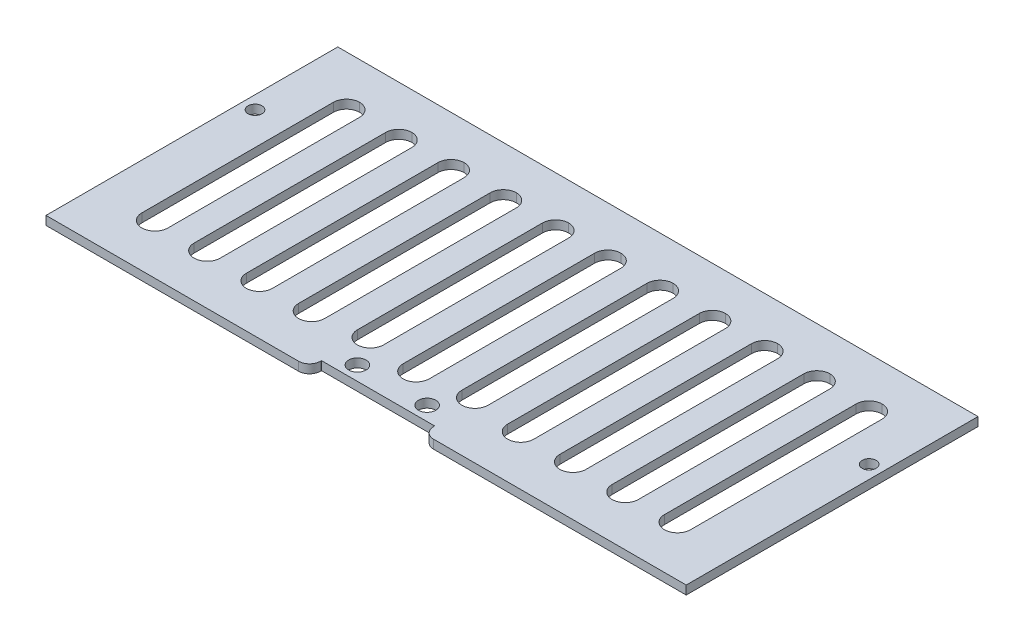
SolidWorks part; units mm, degrees
ref_plane "前视基准面" through (0, 0, 0) normal (0, 0, 1) x (1, 0, 0)
ref_plane "上视基准面" through (0, 0, 0) normal (0, 1, 0) x (1, 0, 0)
ref_plane "右视基准面" through (0, 0, 0) normal (1, 0, 0) x (0, 0, -1)
sketch "草图1" plane through (0, 0, 0) normal (0, 1, 0) x (1, 0, 0)
  line L1 (-73.5, 35) -> (73.5, 35)
  line L2 (-73.5, 35) -> (-73.5, -35)
  line L3 (-73.5, -35) -> (73.5, -35)
  line L4 (73.5, 35) -> (73.5, -35)
  line L5 (-73.5, 35) -> (73.5, -35) construction
  line L6 (-73.5, -35) -> (73.5, 35) construction
  point P0 (0, 0)
  dimension "D1" = 70
  dimension "D2" = 147
extrude "凸台-拉伸1" add sketch "草图1" along normal blind 2
sketch "草图3" plane through (0, 2, 0) normal (0, 1, 0) x (1, 0, 0)
  line L0 (73.5, -35) -> (73.5, 35) construction
  line L1 (73.5, 32) -> (-73.5, 32)
  line L2 (73.5, 32) -> (73.5, 35)
  line L3 (73.5, 35) -> (-73.5, 35)
  line L4 (-73.5, 32) -> (-73.5, 35)
  line L5 (-73.5, 35) -> (-73.5, -35) construction
  line L7 (73.5, 35) -> (-73.5, 35) construction
  dimension "D3" = 3
extrude "切除-拉伸1" cut sketch "草图3" against normal through all
sketch "草图5" plane through (0, 2, 0) normal (0, 1, 0) x (1, 0, 0)
  line L0 (0, 0) -> (0, -29) construction
  line L1 (-8, -29) -> (8, -29) construction
  circle A0 centre (-8, -29) radius 2
  circle A1 centre (8, -29) radius 2
  point P6 (0, -29)
  dimension "D3" = 4
  dimension "D4" = 4
  dimension "D1" = 16
  dimension "D2" = 29
extrude "切除-拉伸3" cut sketch "草图5" against normal blind 10
sketch "草图6" plane through (0, 2, 0) normal (0, 1, 0) x (1, 0, 0)
  line L0 (0, 32) -> (0, -35) construction
  line L1 (-73.5, 32) -> (73.5, 32) construction
  line L2 (-73.5, -35) -> (73.5, -35) construction
  line L3 (-73.5, 32) -> (-73.5, -35) construction
  circle A0 centre (-70.5, 10) radius 1.6
  circle A1 centre (70.5, 10) radius 1.6
  dimension "D1" = 3.2
  dimension "D2" = 3
  dimension "D3" = 45
extrude "切除-拉伸4" cut sketch "草图6" against normal blind 10
sketch "草图7" plane through (0, 2, 0) normal (0, 1, 0) x (1, 0, 0)
  line L0 (0, 32) -> (0, -35) construction
  line L1 (-73.5, 32) -> (73.5, 32) construction
  line L2 (-73.5, -35) -> (73.5, -35) construction
  line L3 (9, -25) -> (9, 23.5)
  line L4 (-3, -26.5) -> (3, -26.5)
  line L5 (-3, -26.5) -> (-3, 23.5)
  line L6 (-3, 23.5) -> (3, 23.5)
  line L7 (3, -26.5) -> (3, 23.5)
  line L8 (-3, -26.5) -> (3, 23.5) construction
  line L9 (-3, 23.5) -> (3, -26.5) construction
  line L11 (15, -25) -> (15, 23.5)
  line L12 (9, 23.5) -> (15, 23.5)
  line L13 (21, -26.5) -> (21, 23.5)
  line L14 (21, -26.5) -> (27, -26.5)
  line L15 (27, -26.5) -> (27, 23.5)
  line L16 (21, 23.5) -> (27, 23.5)
  line L17 (33, -26.5) -> (33, 23.5)
  line L18 (33, -26.5) -> (39, -26.5)
  line L19 (39, -26.5) -> (39, 23.5)
  line L20 (33, 23.5) -> (39, 23.5)
  line L21 (45, -26.5) -> (45, 23.5)
  line L22 (45, -26.5) -> (51, -26.5)
  line L23 (51, -26.5) -> (51, 23.5)
  line L24 (45, 23.5) -> (51, 23.5)
  line L25 (57, -26.5) -> (57, 23.5)
  line L26 (57, -26.5) -> (63, -26.5)
  line L27 (63, -26.5) -> (63, 23.5)
  line L28 (57, 23.5) -> (63, 23.5)
  line L29 (-15, -25) -> (-15, 23.5)
  line L31 (-9, -25) -> (-9, 23.5)
  line L32 (-15, 23.5) -> (-9, 23.5)
  line L33 (-27, -26.5) -> (-27, 23.5)
  line L34 (-27, -26.5) -> (-21, -26.5)
  line L35 (-21, -26.5) -> (-21, 23.5)
  line L36 (-27, 23.5) -> (-21, 23.5)
  line L37 (-39, -26.5) -> (-39, 23.5)
  line L38 (-39, -26.5) -> (-33, -26.5)
  line L39 (-33, -26.5) -> (-33, 23.5)
  line L40 (-39, 23.5) -> (-33, 23.5)
  line L41 (-51, -26.5) -> (-51, 23.5)
  line L42 (-51, -26.5) -> (-45, -26.5)
  line L43 (-45, -26.5) -> (-45, 23.5)
  line L44 (-51, 23.5) -> (-45, 23.5)
  line L45 (-63, -26.5) -> (-63, 23.5)
  line L46 (-63, -26.5) -> (-57, -26.5)
  line L47 (-57, -26.5) -> (-57, 23.5)
  line L48 (-63, 23.5) -> (-57, 23.5)
  line L49 (-15, -25) -> (-9, -25)
  line L51 (9, -25) -> (15, -25)
  line L53 (9, -26.5) -> (15, -26.5) [skipped]
  line L54 (-15, -26.5) -> (-9, -26.5) [skipped]
  point P6 (0, -1.5)
  dimension "D1" = 6
  dimension "D2" = 50
  dimension "D3" = 6
  dimension "D4" = 6
  dimension "D6" = 6
  dimension "D7" = 10
  dimension "D5" = 6
extrude "切除-拉伸5" cut sketch "草图7" against normal blind 10
fillet "圆角1" radius 3 44 edges at (-63, 1, -23.5) (-57, 1, -23.5) (-57, 1, 26.5) (-63, 1, 26.5) (-27, 1, -23.5) (-39, 1, -23.5) (-51, 1, -23.5) (-3, 1, -23.5) (-15, 1, -23.5) (9, 1, -23.5) (33, 1, -23.5) (21, 1, -23.5) (45, 1, -23.5) (57, 1, -23.5) (63, 1, -23.5) (51, 1, -23.5) (39, 1, -23.5) (27, 1, -23.5) (15, 1, -23.5) (3, 1, -23.5) (-9, 1, -23.5) (-21, 1, -23.5) (-33, 1, -23.5) (-45, 1, -23.5) (-45, 1, 26.5) (-33, 1, 26.5) (-21, 1, 26.5) (3, 1, 26.5) (27, 1, 26.5) (39, 1, 26.5) (51, 1, 26.5) (63, 1, 26.5) (21, 1, 26.5) (33, 1, 26.5) (45, 1, 26.5) (57, 1, 26.5) (-3, 1, 26.5) (-27, 1, 26.5) (-39, 1, 26.5) (-51, 1, 26.5) (15, 1, 25) (9, 1, 25) (-15, 1, 25) (-9, 1, 25)
sketch "草图8" plane through (0, 2, 0) normal (0, 1, 0) x (1, 0, 0)
  line L0 (-73.5, -35) -> (73.5, -35) construction
  line L1 (-13, -32.25) -> (13, -32.25)
  line L2 (-13, -32.25) -> (-13, -37.75)
  line L3 (-13, -37.75) -> (13, -37.75)
  line L4 (13, -32.25) -> (13, -37.75)
  line L5 (-13, -32.25) -> (13, -37.75) construction
  line L6 (-13, -37.75) -> (13, -32.25) construction
  point P0 (0, -35)
  dimension "D1" = 26
  dimension "D2" = 5.5
extrude "切除-拉伸6" cut sketch "草图8" against normal through all
fillet "圆角2" radius 2.5 2 edges at (13, 1, 35) (-13, 1, 35)
